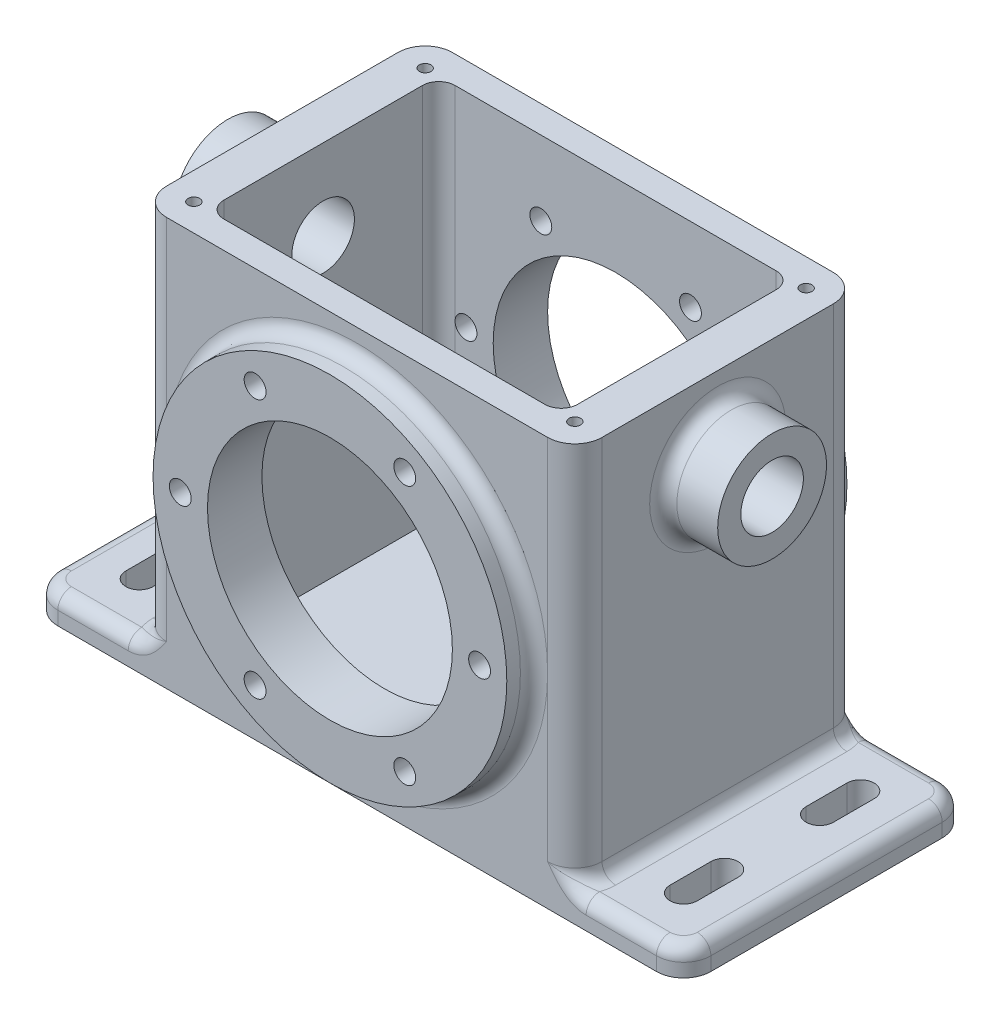
SolidWorks part; units mm, degrees
material "Cast Alloy Steel"
ref_plane "Front Plane" through (0, 0, 0) normal (0, 0, 1) x (1, 0, 0)
ref_plane "Top Plane" through (0, 0, 0) normal (0, 1, 0) x (1, 0, 0)
ref_plane "Right Plane" through (0, 0, 0) normal (1, 0, 0) x (0, 0, -1)
sketch "Sketch1" plane through (0, 0, 0) normal (0, 1, 0) x (1, 0, 0)
  line L0 (-76.2, 33.3375) -> (76.2, -33.3375) construction
  line L2 (-76.2, 33.3375) -> (76.2, 33.3375)
  line L3 (-76.2, 33.3375) -> (-76.2, -33.3375)
  line L4 (-76.2, -33.3375) -> (76.2, -33.3375)
  line L5 (76.2, 33.3375) -> (76.2, -33.3375)
  dimension "D1" = 66.675
  dimension "D2" = 152.4
extrude "Boss-Extrude1" add sketch "Sketch1" along normal blind 6.35
sketch "Sketch2" plane through (0, 6.35, 0) normal (0, 1, 0) x (1, 0, 0)
  line L0 (76.2, 33.3375) -> (-76.2, 33.3375) construction
  line L1 (-50.8, -33.3375) -> (50.8, -33.3375)
  line L2 (-50.8, -33.3375) -> (-50.8, 33.3375)
  line L3 (-50.8, 33.3375) -> (50.8, 33.3375)
  line L4 (50.8, -33.3375) -> (50.8, 33.3375)
  line L5 (-50.8, -33.3375) -> (50.8, 33.3375) construction
  line L6 (-50.8, 33.3375) -> (50.8, -33.3375) construction
  point P0 (0, 0)
  dimension "D1" = 101.6
extrude "Boss-Extrude2" add sketch "Sketch2" along normal blind 88.9
fillet "Fillet1" radius 6.35 8 edges at (-76.2, 3.175, -33.3375) (76.2, 3.175, -33.3375) (76.2, 3.175, 33.3375) (-76.2, 3.175, 33.3375)
fillet "Fillet2" radius 3.175 16 edges at (74.3401, 6.35, 31.4776) (48.9401, 6.35, 31.4776) (48.9401, 6.35, -31.4776) (74.3401, 6.35, -31.4776) (76.2, 6.35, 0) (-48.9401, 6.35, -31.4776) (-48.9401, 6.35, 31.4776) (-74.3401, 6.35, 31.4776) (-76.2, 6.35, 0) (-74.3401, 6.35, -31.4776)
sketch "Sketch3" plane through (0, 95.25, 0) normal (0, 1, 0) x (1, 0, 0)
  line L1 (-37.465, 26.9875) -> (37.465, 26.9875)
  line L2 (-41.275, 23.1775) -> (-41.275, -23.1775)
  line L3 (-37.465, -26.9875) -> (37.465, -26.9875)
  line L4 (41.275, 23.1775) -> (41.275, -23.1775)
  line L5 (50.8, -26.9875) -> (50.8, 26.9875) construction
  line L6 (44.45, 33.3375) -> (-44.45, 33.3375) construction
  line L7 (-44.45, -33.3375) -> (44.45, -33.3375) construction
  line L8 (-50.8, 26.9875) -> (-50.8, -26.9875) construction
  arc A0 (37.465, -26.9875) -> (41.275, -23.1775) centre (37.465, -23.1775) ccw
  arc A1 (37.465, 26.9875) -> (41.275, 23.1775) centre (37.465, 23.1775) cw
  arc A2 (-37.465, 26.9875) -> (-41.275, 23.1775) centre (-37.465, 23.1775) ccw
  arc A3 (-41.275, -23.1775) -> (-37.465, -26.9875) centre (-37.465, -23.1775) ccw
  dimension "D5" = 3.81
  dimension "D1" = 9.525
  dimension "D2" = 6.35
  dimension "D3" = 6.35
  dimension "D4" = 9.525
extrude "Top Cut" cut sketch "Sketch3" against normal blind 88.9
sketch "Sketch4" plane through (0, 0, 33.3375) normal (0, 0, 1) x (1, 0, 0)
  line L0 (-44.45, 95.25) -> (44.45, 95.25) construction
  circle A0 centre (0, 47.625) radius 41.275
  dimension "D2" = 82.55
  dimension "D1" = 47.625
extrude "Front Boss" add sketch "Sketch4" along normal blind 6.35
mirror "Mirror1" about plane through (0, 0, 0) normal (0, 0, 1) of "Front Boss"
sketch "Sketch5" plane through (50.8, 0, 0) normal (1, 0, 0) x (0, 0, -1)
  line L0 (-26.9875, 95.25) -> (26.9875, 95.25) construction
  circle A0 centre (0, 76.2) radius 12.7
  dimension "D2" = 25.4
  dimension "D1" = 19.05
extrude "Side Boss" add sketch "Sketch5" along normal blind 12.7
mirror "Mirror2" about plane through (0, 0, 0) normal (1, 0, 0) of "Side Boss"
sketch "Sketch6" plane through (0, 0, 39.6875) normal (0, 0, 1) x (1, 0, 0)
  circle A0 centre (0, 47.625) radius 28.575
  circle A2 centre (0, 47.625) radius 41.275 construction
  dimension "D1" = 57.15
extrude "Cut-Extrude2" cut sketch "Sketch6" against normal through all
sketch "Sketch7" plane through (63.5, 0, 0) normal (1, 0, 0) x (0, 0, -1)
  circle A0 centre (0, 76.2) radius 7.3025
  dimension "D1" = 14.605
extrude "Shaft Hole" cut sketch "Sketch7" against normal through all
hole_wizard "1/4-20 Tapped Hole1" positions "Sketch9" profile "Sketch8" tap size "1/4-20" standard "ANSI Inch" end condition up to next
sketch "Sketch9" plane through (0, 0, 39.6875) normal (0, 0, 1) x (1, 0, 0)
  line L0 (41.275, 47.625) -> (28.575, 47.625) construction
  circle A0 centre (0, 47.625) radius 41.275 construction
  circle A1 centre (0, 47.625) radius 41.275 construction
  circle A2 centre (0, 47.625) radius 28.575 construction
  point P12 (34.925, 47.625)
sketch "Sketch8" plane through (34.925, 47.625, 39.6875) normal (1, 0, 0) x (0, -1, 0)
  line L0 (0, 0) -> (0, 12.7)
  line L1 (0, 12.7) -> (2.5527, 12.7)
  line L2 (2.5527, 12.7) -> (2.5527, 0)
  line L5 (2.5527, 0) -> (0, 0)
  line L11 (0, -6.35) -> (0, 107.95) construction
  dimension "Thru Tap Drill Dia." = 5.1054
  dimension "Thru Tap Drill Depth" = 12.7
cosmetic thread "Hole Thread1" parameters "D2"=6.35
pattern_circular "CirPattern1" count 6 over 360 about axis through (0, 47.625, 39.6875) along (0, 0, 1) of "1/4-20 Tapped Hole1"
mirror "Mirror3" about plane through (0, 0, 0) normal (0, 0, 1) of "CirPattern1"
hole_wizard "#6-32 Tapped Hole1" positions "Sketch12" profile "Sketch10" tap size "#6-32" standard "ANSI Inch"
sketch "Sketch12" plane through (0, 95.25, 0) normal (0, 1, 0) x (1, 0, 0)
  point P0 (-44.45, -26.9875)
  point P3 (-44.45, 26.9875)
  point P6 (44.45, 26.9875)
  point P9 (44.45, -26.9875)
sketch "Sketch10" plane through (-44.45, 95.25, 26.9875) normal (1, 0, 0) x (0, 0, 1)
  line L0 (0, 0) -> (0, 11.7855)
  line L1 (0, 11.7855) -> (1.3525, 10.9728)
  line L2 (1.3525, 10.9728) -> (1.3525, 0)
  line L5 (1.3525, 0) -> (0, 0)
  line L10 (0, 11.7855) -> (-1.3525, 10.9728) construction
  line L11 (0, -6.35) -> (0, 107.95) construction
  dimension "Tap Drill Dia." = 2.7051
  dimension "Tap Drill Depth" = 10.9728
  dimension "Drill Angle" = 118
cosmetic thread "Hole Thread2" parameters "D1"=7.0104, "D2"=3.5052
cosmetic thread "Hole Thread3" parameters "D1"=7.0104, "D2"=3.5052
cosmetic thread "Hole Thread4" parameters "D1"=7.0104, "D2"=3.5052
cosmetic thread "Hole Thread5" parameters "D1"=7.0104, "D2"=3.5052
sketch "Sketch13" plane through (0, 6.35, 0) normal (0, 1, 0) x (1, 0, 0)
  line L0 (-63.5, -20.6375) -> (-63.5, -11.1125) construction
  line L1 (-66.675, -20.6375) -> (-66.675, -11.1125)
  line L2 (-60.325, -20.6375) -> (-60.325, -11.1125)
  line L3 (-76.2, -26.9875) -> (-76.2, 26.9875) construction
  line L4 (-53.4303, -33.3375) -> (-69.85, -33.3375) construction
  arc A0 (-66.675, -20.6375) -> (-60.325, -20.6375) centre (-63.5, -20.6375) ccw
  arc A1 (-60.325, -11.1125) -> (-66.675, -11.1125) centre (-63.5, -11.1125) ccw
  point P2 (-63.5, -15.875)
  dimension "D4" = 12.7
  dimension "D1" = 6.35
  dimension "D2" = 9.525
  dimension "D3" = 12.7
extrude "Slot" cut sketch "Sketch13" against normal through all
pattern_linear "LPattern1" count 2 spacing 31.75 along (0, 0, -1) of "Slot"
mirror "Mirror4" about plane through (0, 0, 0) normal (1, 0, 0) of "LPattern1"
fillet "Fillet3" radius 3.175 4 edges at (-41.275, 47.625, 33.3375) (41.275, 47.625, -33.3375) (50.8, 76.2, 12.7) (-50.8, 76.2, -12.7)
